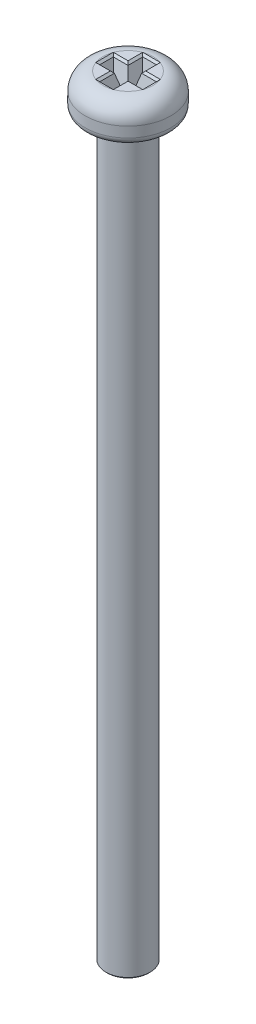
SolidWorks part; units mm, degrees
ref_plane "Спереди" through (0, 0, 0) normal (0, 0, 1) x (1, 0, 0)
ref_plane "Сверху" through (0, 0, 0) normal (0, 1, 0) x (1, 0, 0)
ref_plane "Справа" through (0, 0, 0) normal (1, 0, 0) x (0, 0, -1)
sketch "Эскиз1" plane through (0, 0, 0) normal (0, 0, 1) x (1, 0, 0)
  line L0 (0, 0) -> (0, 52.4) construction
  line L1 (2.9, 52.4) -> (2.9, 50)
  line L2 (2.9, 50) -> (1.5, 50)
  line L3 (1.5, 50) -> (1.5, 0)
  line L4 (1.5, 0) -> (0, 0)
  line L5 (2.9, 52.4) -> (0, 52.4)
  line L6 (0, 0) -> (0, 52.4)
  dimension "D1" = 50
  dimension "D2" = 1.5
  dimension "D3" = 2.4
  dimension "D4" = 2.9
revolve "Повернуть1" add sketch "Эскиз1" angle 360 about L0
fillet "Скругление1" radius 1.2 1 edges at (0, 52.4, -2.9)
fillet "Скругление2" radius 0.5 1 edges at (0, 50, -2.9)
sketch "Эскиз2" plane through (0, 52.4, 0) normal (0, 1, 0) x (1, 0, 0)
  line L0 (0.5, -0.5) -> (0.5, -1.5)
  line L1 (-1.5, 0.5) -> (-0.5, 0.5)
  line L2 (-1.5, 0.5) -> (-1.5, -0.5)
  line L3 (-1.5, -0.5) -> (-0.5, -0.5)
  line L4 (1.5, 0.5) -> (1.5, -0.5)
  line L5 (-0.5, 1.5) -> (0.5, 1.5)
  line L6 (-0.5, 1.5) -> (-0.5, 0.5)
  line L7 (-0.5, -1.5) -> (0.5, -1.5)
  line L8 (0.5, 1.5) -> (0.5, 0.5)
  line L9 (0.5, 0.5) -> (1.5, 0.5)
  line L10 (-0.5, -0.5) -> (-0.5, -1.5)
  line L11 (0.5, -0.5) -> (1.5, -0.5)
  circle A0 centre (0, 0) radius 1.7 construction
  dimension "D1" = 0.5
  dimension "D2" = 0.5
  dimension "D3" = 0.5
  dimension "D4" = 0.5
  dimension "D5" = 1.5
  dimension "D6" = 1.5
  dimension "D7" = 1.5
  dimension "D8" = 1.5
extrude "Вырез-Вытянуть1" cut sketch "Эскиз2" against normal blind 1.5 draft 15
chamfer "Фаска1" distance 0.1 angle 45 12 edges at (-1, 52.4, 0.5) (-0.5, 52.4, 1) (0, 52.4, 1.5) (0.5, 52.4, 1) (1, 52.4, 0.5) (1.5, 52.4, 0) (1, 52.4, -0.5) (0.5, 52.4, -1) (0, 52.4, -1.5) (-0.5, 52.4, -1) (-1.5, 52.4, 0) (-1, 52.4, -0.5) first distance on face at (0, 52.4, 0)
chamfer "Фаска2" distance 0.1 angle 45 1 edges at (0, 0, -1.5)
